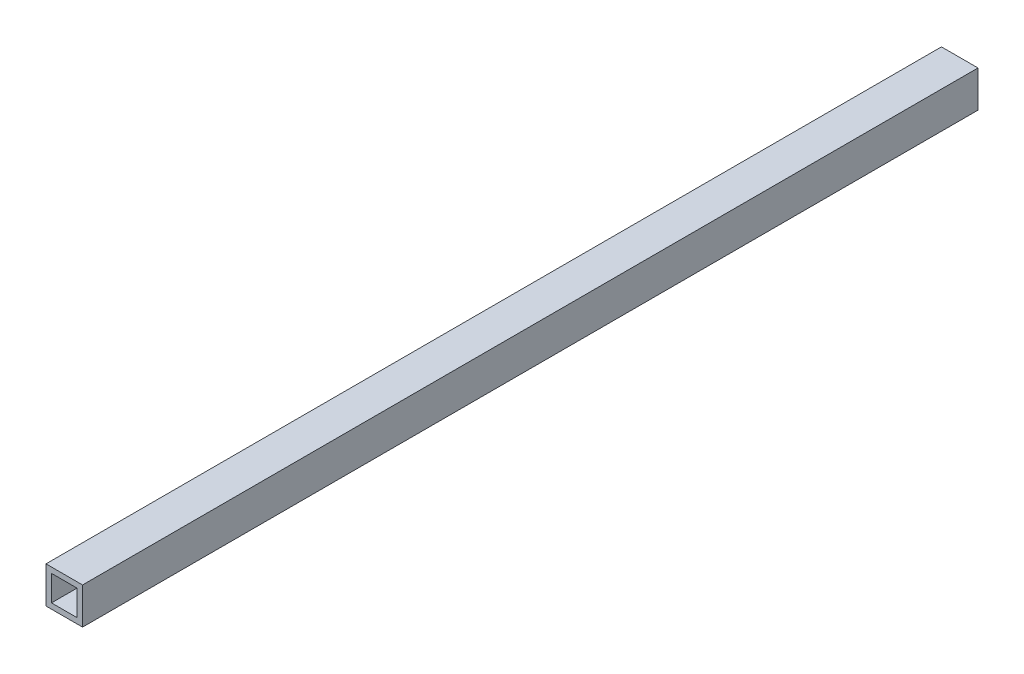
SolidWorks part; units mm, degrees
ref_plane "前视基准面" through (0, 0, 0) normal (0, 0, 1) x (1, 0, 0)
ref_plane "上视基准面" through (0, 0, 0) normal (0, 1, 0) x (1, 0, 0)
ref_plane "右视基准面" through (0, 0, 0) normal (1, 0, 0) x (0, 0, -1)
other "Configuration Table"
sketch "草图1" plane through (0, 0, 0) normal (0, 0, 1) x (1, 0, 0)
  line L0 (-9.3333, 11.0061) -> (-9.3333, -8.9939)
  line L1 (-9.3333, 11.0061) -> (10.6667, 11.0061)
  line L2 (-9.3333, -8.9939) -> (10.6667, -8.9939)
  line L3 (10.6667, 11.0061) -> (10.6667, -8.9939)
  dimension "D1" = 20
  dimension "D2" = 20
extrude "凸台-拉伸1" add sketch "草图1" along normal blind 490
sketch "草图2" plane through (0, 0, 0) normal (0, 0, -1) x (-1, 0, 0)
  line L0 (-10.6667, -8.9939) -> (-10.6667, 11.0061) construction
  line L1 (-7.6667, 8.0061) -> (6.3333, 8.0061)
  line L2 (-7.6667, 8.0061) -> (-7.6667, -5.9939)
  line L3 (-7.6667, -5.9939) -> (6.3333, -5.9939)
  line L4 (6.3333, 8.0061) -> (6.3333, -5.9939)
  line L5 (9.3333, 11.0061) -> (9.3333, -8.9939) construction
  line L6 (9.3333, -8.9939) -> (-10.6667, -8.9939) construction
  line L7 (-10.6667, 11.0061) -> (9.3333, 11.0061) construction
  dimension "D1" = 3
  dimension "D2" = 3
  dimension "D3" = 3
  dimension "D4" = 3
extrude "切除-拉伸1" cut sketch "草图2" against normal through all
